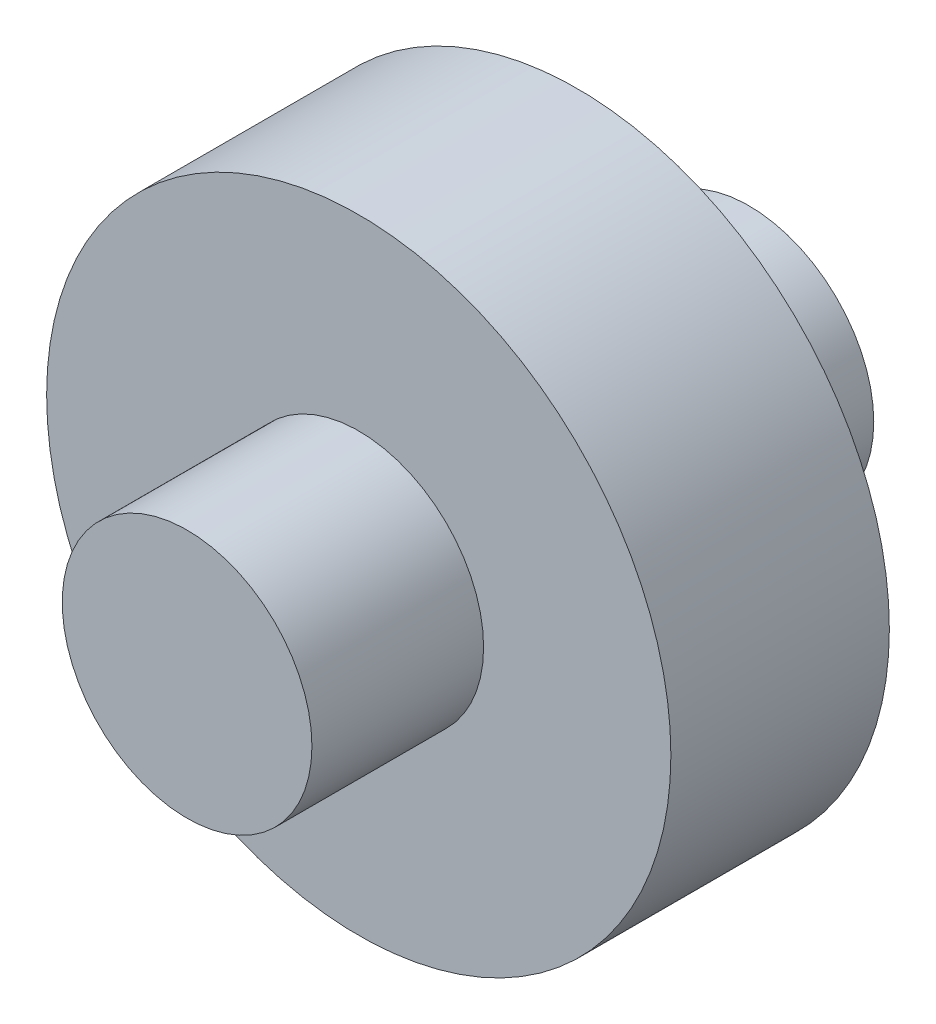
SolidWorks part; units mm, degrees
ref_plane "前视基准面" through (0, 0, 0) normal (0, 0, 1) x (1, 0, 0)
ref_plane "上视基准面" through (0, 0, 0) normal (0, 1, 0) x (1, 0, 0)
ref_plane "右视基准面" through (0, 0, 0) normal (1, 0, 0) x (0, 0, -1)
sketch "草图1" plane through (0, 0, 0) normal (0, 0, 1) x (1, 0, 0)
  circle A0 centre (0, 0) radius 10
  circle A1 centre (0, 0) radius 4
extrude "凸台-拉伸2" add sketch "草图1" along normal mid plane 18 contours A1
extrude "凸台-拉伸3" add sketch "草图1<6>" along normal mid plane 7
sketch "草图1<6>" plane through (0, 0, 0) normal (0, 0, 1) x (1, 0, 0) same geometry as "草图1"
